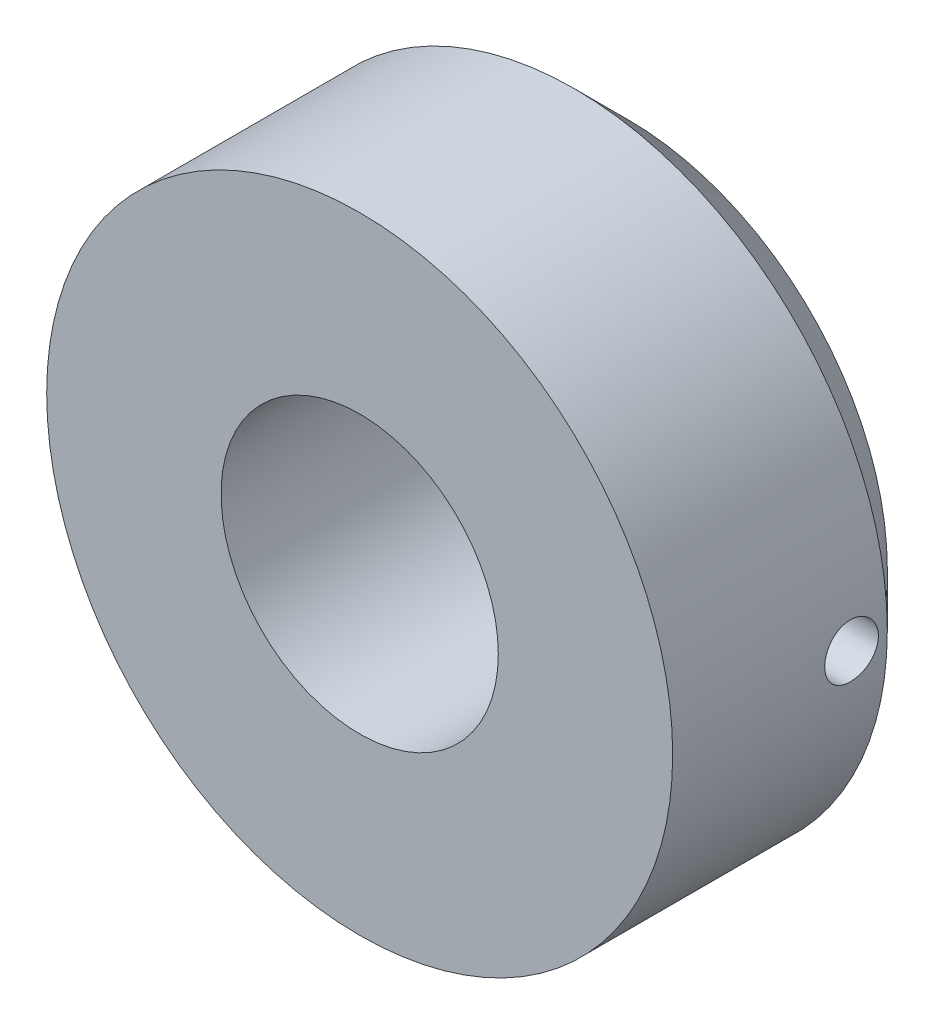
SolidWorks part; units mm, degrees
ref_plane "Front Plane" through (0, 0, 0) normal (0, 0, 1) x (1, 0, 0)
ref_plane "Top Plane" through (0, 0, 0) normal (0, 1, 0) x (1, 0, 0)
ref_plane "Right Plane" through (0, 0, 0) normal (1, 0, 0) x (0, 0, -1)
ref_axis "Z" through (0, 0, 543.0939) along (0, 0, -1)
ref_axis "X" through (17.0818, 0, 0) along (-1, 0, 0)
ref_axis "Y" through (0, 33, 0) along (0, -1, 0)
sketch "Sketch1" plane through (0, 0, 0) normal (0, 0, 1) x (1, 0, 0)
  circle A0 centre (0, 0) radius 17.5
  circle A1 centre (0, 0) radius 8.75
  dimension "D1" = 35
  dimension "D2" = 17.5
extrude "Boss-Extrude1" add sketch "Sketch1" against normal blind 5 and the other way blind 10
sketch "Sketch2" plane through (0, 0, 0) normal (0, 1, 0) x (1, 0, 0)
  line L0 (-33, 0) -> (33, 0) construction
  line L1 (0, -8.25) -> (0, 8.25) construction
  circle A0 centre (0, 0) radius 1.5
  dimension "D1" = 3
extrude "Cut-Extrude1" cut sketch "Sketch2" against normal through all
sketch "Sketch3" plane through (0, 0, 0) normal (1, 0, 0) x (0, 0, -1)
  circle A0 centre (0, 0) radius 1.5
  dimension "D1" = 3
extrude "Cut-Extrude2" cut sketch "Sketch3" along normal through all
chamfer "Chamfer1" distance 3 angle 45 1 edges at (17.5, 0, -5)
sketch "Sketch4" plane through (0, 0, 0) normal (0, 0, 1) x (1, 0, 0)
  circle A0 centre (0, 0) radius 8.75
  circle A2 centre (0, 0) radius 8.75 construction
  circle A3 centre (0, 0) radius 7.75
  dimension "D1" = 1
extrude "Boss-Extrude2" add sketch "Sketch4" along normal up to surface and the other way up to surface up to face at (17.5, 0, 10) other way up to face at (14.5, 0, -5)
equation "\"EyeDiameter\" = 35"
equation "\"BasePlaneDistance\" = \"EyeDiameter\"/2+19.84"
equation "\"EyeClearance\" = 2"
equation "\"EyeOD\"= \"EyeDiameter\""
equation "\"D1@Sketch1\"=\"EyeOD\""
equation "\"D2@Sketch1\"=\"EyeDiameter\"*0.5"
equation "\"pinHoleDiameter\"= 3"
equation "\"D1@Sketch2\"=\"pinHoleDiameter\""
equation "\"D1@Sketch3\"=\"pinHoleDiameter\""
